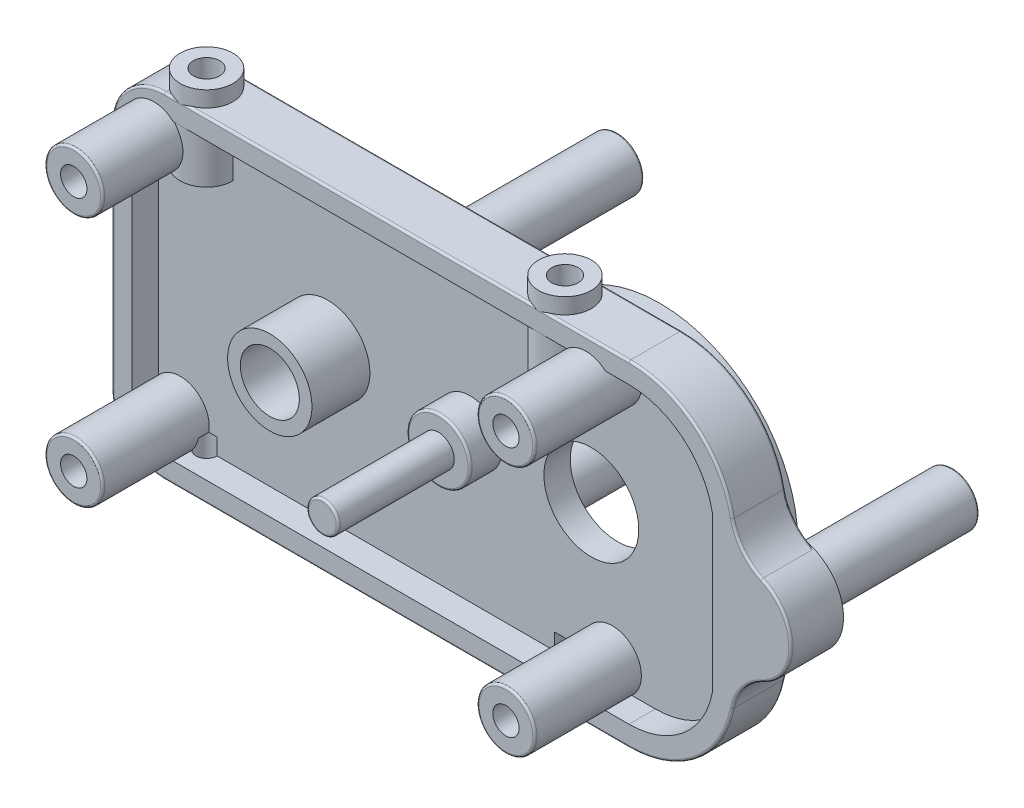
SolidWorks part; units mm, degrees
note: The reader was unsure of these and kept them because the rebuilt part matched: shared geometry of "草图23<3>".
ref_plane "前视基准面" through (0, 0, 0) normal (0, 0, 1) x (1, 0, 0)
ref_plane "上视基准面" through (0, 0, 0) normal (0, 1, 0) x (1, 0, 0)
ref_plane "右视基准面" through (0, 0, 0) normal (1, 0, 0) x (0, 0, -1)
sketch "草图1" plane through (0, 0, 0) normal (0, 0, 1) x (1, 0, 0)
  line L0 (0, 16) -> (50, 16) construction
  line L1 (0, 0.1) -> (50, 0.1)
  line L2 (0, 0.1) -> (0, 31.9)
  line L3 (0, 31.9) -> (50, 31.9)
  line L4 (50, 0.1) -> (59.0704, 0.1)
  line L5 (50, 31.9) -> (59.0704, 31.9)
  line L6 (59.0704, 31.9) -> (59.0704, 20.2477)
  line L7 (59.0704, 20.2477) -> (61.6342, 20.2477)
  line L8 (59.0704, 11.7523) -> (61.6342, 11.7523)
  line L9 (59.0704, 0.1) -> (59.0704, 11.7523)
  line L10 (45, 27.9) -> (45, -2.3835) construction
  circle A0 centre (4, 27.9) radius 1.5 construction
  circle A1 centre (45, 27.9) radius 1.5 construction
  circle A2 centre (45, 4.1) radius 1.5 construction
  circle A3 centre (4, 4.1) radius 1.5 construction
  circle A4 centre (18, 16.1) radius 2.8
  circle A5 centre (43, 16) radius 4.5
  arc A7 (61.6342, 11.7523) -> (61.6342, 20.2477) centre (59.8, 16) ccw
  arc A8 (58.895, 20.3918) -> (60.5407, 19.7498) centre (60.5678, 22.2496) ccw construction
  circle A14 centre (59.8, 16) radius 1.6 construction
  point P22 (38.5, 16)
  dimension "D3" = 3
  dimension "D10" = 18
  dimension "D11" = 5.6
  dimension "D14" = 9
  dimension "D8" = 43
  dimension "D1" = 50
  dimension "D2" = 31.8
  dimension "D6" = 4
  dimension "D7" = 4
  dimension "D9" = 4
  dimension "D12" = 4
  dimension "D13" = 41
  dimension "D15" = 16.8
  dimension "D16" = 23.8
  dimension "D4" = 2
  dimension "D5" = 2
extrude "凸台-拉伸1" add sketch "草图1" along normal blind 5
sketch "草图3" plane through (0, 0, 0) normal (0, 0, -1) x (-1, 0, 0)
  circle A0 centre (-43, 16) radius 11.1
  circle A1 centre (-43, 16) radius 13.1
  dimension "D1" = 22.2
  dimension "D2" = 2
extrude "凸台-拉伸2" add sketch "草图3" along normal blind 4
fillet "圆角1" radius 10 2 edges at (59.0704, 0.1, 2.5) (59.0704, 31.9, 2.5)
fillet "圆角2" radius 5 2 edges at (59.0704, 11.7523, 2.5) (59.0704, 20.2477, 2.5)
fillet "圆角3" radius 5 2 edges at (0, 0.1, 2.5) (0, 31.9, 2.5)
sketch "草图4" plane through (0, 0, 5) normal (0, 0, 1) x (1, 0, 0)
  line L3 (56.9731, 23.4329) -> (56.9731, 8.5671)
  line L6 (1.95, 26.9) -> (1.95, 5.1)
  line L7 (5, 2.05) -> (49.0704, 2.05)
  line L8 (49.0704, 29.95) -> (5, 29.95)
  line L9 (1.95, 26.9) -> (1.95, 5.1)
  line L10 (5, 2.05) -> (49.0704, 2.05)
  line L11 (49.0704, 29.95) -> (5, 29.95)
  arc A14 (1.95, 5.1) -> (5, 2.05) centre (5, 5.1) ccw
  arc A15 (49.0704, 2.05) -> (56.9731, 8.5671) centre (49.0704, 10.1) ccw
  arc A16 (60.9881, 13.6013) -> (56.9731, 8.5671) centre (63.7959, 7.2437) ccw
  arc A17 (60.9881, 13.6013) -> (60.9881, 18.3987) centre (59.8, 16) ccw
  arc A18 (56.9731, 23.4329) -> (60.9881, 18.3987) centre (63.7959, 24.7563) ccw
  arc A19 (56.9731, 23.4329) -> (49.0704, 29.95) centre (49.0704, 21.9) ccw
  arc A20 (5, 29.95) -> (1.95, 26.9) centre (5, 26.9) ccw
  arc A21 (1.95, 5.1) -> (5, 2.05) centre (5, 5.1) ccw
  arc A22 (49.0704, 2.05) -> (56.9731, 8.5671) centre (49.0704, 10.1) ccw
  arc A26 (56.9731, 23.4329) -> (49.0704, 29.95) centre (49.0704, 21.9) ccw
  arc A27 (5, 29.95) -> (1.95, 26.9) centre (5, 26.9) ccw
  dimension "D1" = 1.95
extrude "切除-拉伸1" cut sketch "草图4" against normal blind 2.5
sketch "草图5" plane through (0, 0, 2.5) normal (0, 0, 1) x (1, 0, 0)
  circle A0 centre (45, 27.9) radius 1.5 construction
  circle A1 centre (45, 4.1) radius 1.5 construction
  circle A2 centre (4, 4.1) radius 1.5 construction
  circle A3 centre (4, 27.9) radius 1.5 construction
  circle A8 centre (45, 4.1) radius 1.5 construction
  circle A9 centre (45, 27.9) radius 1.5 construction
  circle A10 centre (4, 27.9) radius 1.5 construction
  circle A11 centre (4, 4.1) radius 1.5 construction
  circle A12 centre (45, 4.1) radius 2.75
  circle A13 centre (45, 27.9) radius 2.75
  circle A14 centre (4, 27.9) radius 2.75
  circle A15 centre (4, 4.1) radius 2.75
  dimension "D1" = 1.25
extrude "凸台-拉伸3" add sketch "草图5" along normal blind 10.1
sketch "草图6" plane through (0, 0, 2.5) normal (0, 0, 1) x (1, 0, 0)
  circle A0 centre (18, 16.1) radius 2.8 construction
  circle A1 centre (18, 16.1) radius 2.8
  circle A2 centre (18, 16.1) radius 4
  dimension "D1" = 1.2
extrude "凸台-拉伸4" add sketch "草图6" along normal blind 5.5
sketch "草图7" plane through (0, 0, 2.5) normal (0, 0, 1) x (1, 0, 0)
  line L0 (0, 16) -> (50, 16) construction
  line L1 (31.4996, 16) -> (43, 16) construction
  circle A0 centre (31.4996, 16) radius 3
  circle A1 centre (31.4996, 16) radius 1.5
  dimension "D1" = 6
  dimension "D3" = 13.5
  dimension "D2" = 1.5
extrude "凸台-拉伸5" add sketch "草图7" along normal blind 3
hole_wizard "M3 螺纹孔1" positions "草图9" profile "草图8" tap size "M3" standard "Gb"
sketch "草图9" plane through (0, 0, 12.6) normal (0, 0, 1) x (1, 0, 0)
  point P0 (4, 27.9)
  point P3 (4, 4.1)
  point P6 (45, 4.1)
  point P9 (45, 27.9)
sketch "草图8" plane through (4, 27.9, 12.6) normal (1, 0, 0) x (0, -1, 0)
  line L0 (0, 0) -> (0, 7.2511)
  line L1 (0, 7.2511) -> (1.25, 6.5)
  line L2 (1.25, 6.5) -> (1.25, 0)
  line L5 (1.25, 0) -> (0, 0)
  line L10 (0, 7.2511) -> (-1.25, 6.5) construction
  line L11 (0, -6.35) -> (0, 107.95) construction
  dimension "螺纹孔钻头直径" = 2.5
  dimension "螺纹孔钻头深度" = 6.5
  dimension "导头角度" = 118
cosmetic thread "孔螺蚊线1" parameters "D1"=4, "D2"=3
cosmetic thread "孔螺蚊线2" parameters "D1"=4, "D2"=3
cosmetic thread "孔螺蚊线3" parameters "D1"=4, "D2"=3
cosmetic thread "孔螺蚊线4" parameters "D1"=4, "D2"=3
ref_plane "基准面1" through (0, -1.4, 0) normal (0, -1, 0) x (-1, 0, 0)
sketch "草图10" plane through (0, -1.4, 0) normal (0, -1, 0) x (-1, 0, 0)
  line L0 (-5, -5) -> (-49.0704, -5) construction
  circle A0 centre (-6.5, -2.5) radius 2.5
  circle A1 centre (-40.5, -2.5) radius 2.5
  circle A2 centre (-40.5, -2.5) radius 1.25 construction
  circle A3 centre (-6.5, -2.5) radius 1.25 construction
  dimension "D1" = 5
  dimension "D2" = 5
  dimension "D3" = 6.5
  dimension "D4" = 34
  dimension "D5" = 1.25
  dimension "D6" = 1.25
sketch "草图12" plane through (0, 0, 0) normal (0, 0, -1) x (-1, 0, 0)
  line L0 (-7.0896, 16) -> (-52.5795, 16) construction
  line L1 (-52.5795, 16) -> (-67.1558, 16) construction
  line L2 (-43, 11.5) -> (-43, 20.5) construction
  circle A0 centre (-59.8, 16) radius 2.5
  circle A1 centre (-27.9966, 27.65) radius 2.5
  circle A2 centre (-27.9966, 4.35) radius 2.5
  circle A3 centre (-43, 16) radius 4.5 construction
  dimension "D1" = 5
  dimension "D2" = 5
  dimension "D3" = 5
  dimension "D4" = 23.3
  dimension "D5" = 33.87
extrude "凸台-拉伸7" add sketch "草图12" along normal blind 15
fillet "圆角4" radius 0.5 3 edges at (30.4966, 27.65, 0) (30.4966, 4.35, 0) (62.3, 16, 0)
hole_wizard "M3 螺纹孔2" positions "草图14" profile "草图13" tap size "M3" standard "Gb"
sketch "草图14" plane through (0, 0, -15) normal (0, 0, -1) x (-1, 0, 0)
  point P0 (-59.8, 16)
  point P3 (-27.9966, 27.65)
  point P6 (-27.9966, 4.35)
sketch "草图13" plane through (59.8, 16, -15) normal (1, 0, 0) x (0, 1, 0)
  line L0 (0, 0) -> (0, 7.2511)
  line L1 (0, 7.2511) -> (1.25, 6.5)
  line L2 (1.25, 6.5) -> (1.25, 0)
  line L5 (1.25, 0) -> (0, 0)
  line L10 (0, 7.2511) -> (-1.25, 6.5) construction
  line L11 (0, -6.35) -> (0, 107.95) construction
  dimension "螺纹孔钻头直径" = 2.5
  dimension "螺纹孔钻头深度" = 6.5
  dimension "导头角度" = 118
cosmetic thread "孔螺蚊线5" parameters "D1"=4, "D2"=3
cosmetic thread "孔螺蚊线6" parameters "D1"=4, "D2"=3
cosmetic thread "孔螺蚊线7" parameters "D1"=4, "D2"=3
fillet "圆角5" radius 0.2 3 edges at (25.4966, 4.35, -15) (25.4966, 27.65, -15) (57.3, 16, -15)
fillet "圆角6" radius 0.2 4 edges at (6.75, 27.9, 12.6) (47.75, 27.9, 12.6) (47.75, 4.1, 12.6) (6.75, 4.1, 12.6)
fillet "圆角7" radius 0.2 1 edges at (34.4996, 16, 5.5)
fillet "圆角9" radius 0.2 10 edges at (27.0352, 0.1, 5) (1.4645, 1.5645, 5) (0, 16, 5) (1.4645, 30.4355, 5) (27.0352, 31.9, 5) (55.4327, 29.615, 5) (59.8388, 21.7, 5) (64.4268, 16, 5) (59.8388, 10.3, 5) (55.4327, 2.385, 5)
fillet "圆角10" radius 0.2 9 edges at (27.0352, 31.9, 0) (1.4645, 30.4355, 0) (0, 16, 0) (1.4645, 1.5645, 0) (27.0352, 0.1, 0) (55.4327, 2.385, 0) (59.8388, 10.3, 0) (59.8388, 21.7, 0) (55.4327, 29.615, 0)
ref_plane "基准面2" through (0, 33.4, 0) normal (0, 1, 0) x (1, 0, 0)
sketch "草图16" plane through (0, 33.4, 0) normal (0, 1, 0) x (1, 0, 0)
  line L0 (0, -2.5) -> (12.2538, -2.5) construction
  line L1 (0, -4.8) -> (0, -0.2) construction
  line L2 (34, -2.5) -> (46.2538, -2.5) construction
  circle A0 centre (6.5, -2.5) radius 2.5
  circle A1 centre (6.5, -2.5) radius 1 construction
  circle A2 centre (40.5, -2.5) radius 2.5
  circle A3 centre (40.5, -2.5) radius 1 construction
  dimension "D1" = 5
  dimension "D2" = 6.5
  dimension "D3" = 1.5
  dimension "D4" = 2
extrude "凸台-拉伸8" add sketch "草图16" against normal blind 8
sketch "草图17" plane through (0, 33.4, 0) normal (0, 1, 0) x (1, 0, 0)
  circle A0 centre (6.5, -2.5) radius 1 construction
  circle A1 centre (40.5, -2.5) radius 1 construction
  circle A2 centre (6.5, -2.5) radius 1
  circle A3 centre (40.5, -2.5) radius 1
extrude "切除-拉伸3" cut sketch "草图17" against normal blind 5
sketch "草图23" plane through (0, -1.4, 0) normal (0, -1, 0) x (-1, 0, 0)
  line L0 (0, -0.2) -> (0, -4.8) construction
  line L1 (0, -0.2) -> (0, -4.8) construction
  line L2 (0, -2.5) -> (-15.9312, -2.5) construction
  line L4 (-23.5, 1.6992) -> (-23.5, -8.5684) construction
  circle A0 centre (-6.5, -2.5) radius 2.5
  circle A1 centre (-6.5, -2.5) radius 1
  circle A2 centre (-40.5, -2.5) radius 1
  circle A3 centre (-40.5, -2.5) radius 2.5
  dimension "D1" = 5
  dimension "D2" = 1.5
  dimension "D3" = 6.5
  dimension "D4" = 17
extrude "凸台-拉伸9" [suppressed] add sketch "草图23" against normal blind 8 contours A0 A1 | A1 | A2 | A3 A2
extrude "切除-拉伸4" cut sketch "草图23<3>" against normal blind 5 contours A1 | A2
sketch "草图23<3>" plane through (0, -1.4, 0) normal (0, -1, 0) x (-1, 0, 0) same geometry as "草图23"
hole_wizard "M3 螺纹孔6" [suppressed] positions "3D草图6" profile "草图25" tap size "M3" standard "GB"
sketch3d "3D草图6" [suppressed]
  line L0 (6.5, 3.6, 2.5) -> (6.5, -1.4, 2.5) construction
  line L1 (40.5, 3.6, 2.5) -> (40.5, -1.4, 2.5) construction
  point P17 (6.5, -1.4, 2.5)
  point P19 (40.5, -1.4, 2.5)
sketch "草图25" plane through (6.5, -1.4, 2.5) normal (1, 0, 0) x (0, 0, -1)
  line L0 (0, 0) -> (0, 6.2511)
  line L1 (0, 6.2511) -> (1.25, 5.5)
  line L2 (1.25, 5.5) -> (1.25, 0)
  line L5 (1.25, 0) -> (0, 0)
  line L10 (0, 6.2511) -> (-1.25, 5.5) construction
  line L11 (0, -6.35) -> (0, 107.95) construction
  dimension "螺纹孔钻头直径" = 2.5
  dimension "螺纹孔钻头深度" = 5.5
  dimension "导头角度" = 118
cosmetic thread "孔螺蚊线20" parameters "D1"=4, "D2"=3
cosmetic thread "孔螺蚊线21" parameters "D1"=4, "D2"=3
hole_wizard "M3 螺纹孔7" positions "3D草图7" profile "草图26" tap size "M3" standard "GB"
sketch3d "3D草图7"
  line L0 (40.5, 28.4, 2.5) -> (40.5, 33.4, 2.5) construction
  line L1 (6.5, 28.4, 2.5) -> (6.5, 33.4, 2.5) construction
  point P0 (40.5, 33.4, 2.5)
  point P4 (6.5, 33.4, 2.5)
sketch "草图26" plane through (40.5, 33.4, 2.5) normal (1, 0, 0) x (0, 0, 1)
  line L0 (0, 0) -> (0, 7.2511)
  line L1 (0, 7.2511) -> (1.25, 6.5)
  line L2 (1.25, 6.5) -> (1.25, 0)
  line L5 (1.25, 0) -> (0, 0)
  line L10 (0, 7.2511) -> (-1.25, 6.5) construction
  line L11 (0, -6.35) -> (0, 107.95) construction
  dimension "螺纹孔钻头直径" = 2.5
  dimension "螺纹孔钻头深度" = 6.5
  dimension "导头角度" = 118
cosmetic thread "孔螺蚊线22" parameters "D1"=4, "D2"=3
cosmetic thread "孔螺蚊线23" parameters "D1"=4, "D2"=3
sketch "草图27" plane through (0, 0, 2.5) normal (0, 0, 1) x (1, 0, 0)
  circle A0 centre (31.4996, 16) radius 1.5 construction
  circle A1 centre (31.4996, 16) radius 1.5
extrude "凸台-拉伸10" add sketch "草图27" along normal blind 14
fillet "圆角11" radius 0.2 1 edges at (32.9996, 16, 16.5)
